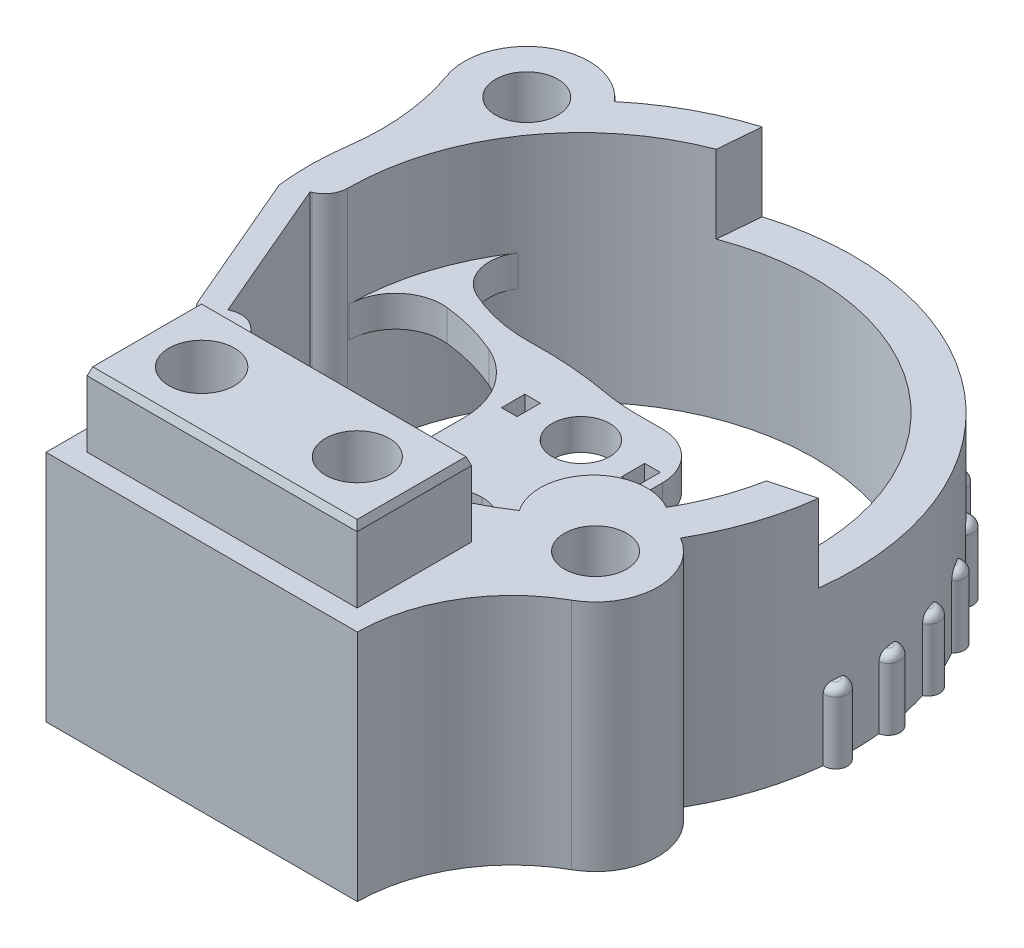
SolidWorks part; units mm, degrees
ref_plane "Спереди" through (0, 0, 0) normal (0, 0, 1) x (1, 0, 0)
ref_plane "Сверху" through (0, 0, 0) normal (0, 1, 0) x (1, 0, 0)
ref_plane "Справа" through (0, 0, 0) normal (1, 0, 0) x (0, 0, -1)
sketch "Sketch1" plane through (0, 0, 0) normal (0, 1, 0) x (1, 0, 0)
  circle A0 centre (0, 0) radius 35
  dimension "D1" = 70
extrude "Boss-Extrude1" add sketch "Sketch1" along normal blind 30
sketch "Sketch6" plane through (0, 30, 0) normal (0, 1, 0) x (1, 0, 0)
  circle A0 centre (0, 0) radius 30
  circle A1 centre (0, 0) radius 35 construction
  dimension "D1" = 5
  dimension "D2" = 60
extrude "Cut-Extrude3" cut sketch "Sketch6" against normal through all
sketch "Sketch7" plane through (0, 30, 0) normal (0, 1, 0) x (1, 0, 0)
  line L0 (0, 0) -> (-22.4976, 26.8116) construction
  line L1 (0, 0) -> (30.3109, -17.5) construction
  line L2 (0, 0) -> (0, -30) construction
  line L3 (0, 0) -> (0, 30) construction
  line L4 (-19.2836, 22.9813) -> (-22.4976, 26.8116)
  line L5 (25.9808, -15) -> (30.3109, -17.5)
  circle A0 centre (0, 0) radius 35 construction
  circle A1 centre (0, 0) radius 30 construction
  arc A2 (-19.2836, 22.9813) -> (25.9808, -15) centre (0, 0) cw
  arc A3 (-22.4976, 26.8116) -> (30.3109, -17.5) centre (0, 0) cw
  dimension "D1" = 40
  dimension "D2" = 60
extrude "Cut-Extrude4" cut sketch "Sketch7" against normal blind 10
sketch "Sketch8" plane through (0, 20, 0) normal (0, 1, 0) x (1, 0, 0)
  line L0 (0, 0) -> (0, -38.8668) construction
  line L3 (10, -33.541) -> (10, 6.459)
  line L4 (10, 6.459) -> (-10, 6.459)
  line L5 (-10, -33.541) -> (-10, 6.459)
  line L6 (10, -33.541) -> (-10, 6.459) construction
  line L7 (10, 6.459) -> (-10, -33.541) construction
  arc A0 (-10, -33.541) -> (10, -33.541) centre (0, 0) ccw
  arc A3 (-22.4976, 26.8116) -> (30.3109, -17.5) centre (0, 0) ccw construction
  point P3 (0, -13.541)
  dimension "D1" = 40
  dimension "D2" = 20
extrude "Boss-Extrude3" add sketch "Sketch8" along normal blind 4 from offset 7 offset against normal yes
sketch "Sketch9" plane through (0, 0, 0) normal (0, -1, 0) x (1, 0, 0)
  line L0 (0, -35) -> (0, 35) construction
  line L2 (-20, 28.7228) -> (20, 28.7228)
  line L3 (-20, 28.7228) -> (-20, 48.7228)
  line L4 (-20, 48.7228) -> (20, 48.7228)
  line L5 (20, 28.7228) -> (20, 48.7228)
  line L6 (-20, 28.7228) -> (20, 48.7228) construction
  line L7 (-20, 48.7228) -> (20, 28.7228) construction
  circle A0 centre (0, 0) radius 35 construction
  point P5 (0, 38.7228)
  dimension "D1" = 40
  dimension "D2" = 20
extrude "Boss-Extrude4" add sketch "Sketch9" against normal up to surface (30 mm away) up to face at (-8.6315, 30, 10.2866)
sketch "Sketch10" plane through (0, 17, 0) normal (0, 1, 0) x (1, 0, 0)
  line L0 (3.7, 0) -> (10, 0) construction
  line L1 (-3.7, 0) -> (-10, 0) construction
  line L2 (8.7, -1.5) -> (6.7, -1.5)
  line L3 (8.7, -1.5) -> (8.7, 1.5)
  line L4 (8.7, 1.5) -> (6.7, 1.5)
  line L5 (6.7, -1.5) -> (6.7, 1.5)
  line L6 (8.7, -1.5) -> (6.7, 1.5) construction
  line L7 (8.7, 1.5) -> (6.7, -1.5) construction
  line L9 (-6.7, -1.5) -> (-8.7, -1.5)
  line L10 (-6.7, -1.5) -> (-6.7, 1.5)
  line L11 (-6.7, 1.5) -> (-8.7, 1.5)
  line L12 (-8.7, -1.5) -> (-8.7, 1.5)
  line L13 (-6.7, -1.5) -> (-8.7, 1.5) construction
  line L14 (-6.7, 1.5) -> (-8.7, -1.5) construction
  circle A0 centre (0, 0) radius 10 construction
  circle A1 centre (0, 0) radius 3.7
  point P6 (7.7, 0)
  point P13 (-7.7, 0)
  dimension "D1" = 20
  dimension "D2" = 7.4
  dimension "D3" = 4
  dimension "D4" = 3
  dimension "D5" = 2
  dimension "D6" = 4
extrude "Cut-Extrude5" cut sketch "Sketch10" against normal through all
sketch "Sketch11" plane through (0, 30, 0) normal (0, 1, 0) x (1, 0, 0)
  line L0 (-20, -38.7228) -> (20, -38.7228) construction
  line L1 (-20, -48.7228) -> (-20, -28.7228) construction
  line L2 (20, -28.7228) -> (20, -48.7228) construction
  circle A0 centre (-10, -38.7228) radius 4.2
  circle A1 centre (10, -38.7228) radius 4.2
  point P10 (0, -38.7228)
  dimension "D1" = 8.4
  dimension "D2" = 20
  dimension "D3" = 10
extrude "Cut-Extrude6" cut sketch "Sketch11" against normal through all
sketch "Sketch15" plane through (0, 30, 0) normal (0, 1, 0) x (1, 0, 0)
  line L0 (19.9782, -38.7228) -> (-20.0306, -38.7228) construction
  line L4 (17.3238, -46.0728) -> (-17.3762, -46.0728)
  line L5 (17.3238, -46.0728) -> (17.3238, -31.3728)
  line L6 (17.3238, -31.3728) -> (-17.3762, -31.3728)
  line L7 (-17.3762, -46.0728) -> (-17.3762, -31.3728)
  line L8 (17.3238, -46.0728) -> (-17.3762, -31.3728) construction
  line L9 (17.3238, -31.3728) -> (-17.3762, -46.0728) construction
  circle A0 centre (-10, -38.7228) radius 4.2
  circle A1 centre (10, -38.7228) radius 4.1
  circle A4 centre (-10, -38.7228) radius 4.2 construction
  point P6 (-0.0262, -38.7228)
  dimension "D1" = 14.7
  dimension "D2" = 34.7
extrude "Boss-Extrude6" add sketch "Sketch15" along normal blind 9.5
chamfer "Chamfer3" distance 1 angle 20 4 edges at (17.3238, 39.5, 38.7228) (-0.0262, 39.5, 46.0728) (-17.3762, 39.5, 38.7228) (-0.0262, 39.5, 31.3728) first distance on face at (17.3238, 34.75, 38.7228) first distance on face at (-0.0262, 34.75, 46.0728) first distance on face at (-17.3762, 34.75, 38.7228) first distance on face at (-0.0262, 34.75, 31.3728)
sketch "Sketch16" plane through (0, 0, 0) normal (0, -1, 0) x (1, 0, 0)
  line L0 (-20, 38.7228) -> (20, 38.7228) construction
  line L1 (-20, 48.7228) -> (-20, 28.7228) construction
  line L2 (20, 28.7228) -> (20, 48.7228) construction
  line L4 (-17.5, 46.2228) -> (17.5, 46.2228)
  line L5 (-17.5, 46.2228) -> (-17.5, 31.2228)
  line L6 (-17.5, 31.2228) -> (17.5, 31.2228)
  line L7 (17.5, 46.2228) -> (17.5, 31.2228)
  line L8 (-17.5, 46.2228) -> (17.5, 31.2228) construction
  line L9 (-17.5, 31.2228) -> (17.5, 46.2228) construction
  point P6 (0, 38.7228)
  dimension "D1" = 15
  dimension "D2" = 35
extrude "Cut-Extrude8" cut sketch "Sketch16" against normal blind 10
chamfer "Chamfer4" distance 1 angle 70 4 edges at (17.5, 0, 38.7228) (0, 0, 46.2228) (-17.5, 0, 38.7228) (0, 0, 31.2228) first distance on face at (0, 0, 38.7228)
sketch "Sketch18" plane through (0, 30, 0) normal (0, 1, 0) x (1, 0, 0)
  line L0 (-31.9117, 14.3752) -> (-22.4976, 26.8116) construction
  line L1 (-22.4976, 26.8116) -> (-19.2836, 22.9813) construction
  line L2 (-31.9117, 14.3752) -> (-27.3529, 12.3216)
  line L3 (-27.3529, 12.3216) -> (-19.2836, 22.9813) construction
  line L4 (-19.2836, 22.9813) -> (-22.4976, 26.8116)
  line L5 (25.9808, -15) -> (30.3109, -17.5) construction
  line L6 (19.6982, -28.9306) -> (16.8841, -24.7977)
  line L7 (25.9808, -15) -> (30.3109, -17.5)
  arc A0 (-22.4976, 26.8116) -> (-31.9117, 14.3752) centre (-28.6259, 21.6693) ccw
  arc A1 (-22.4976, 26.8116) -> (-20, -28.7228) centre (0, 0) ccw construction
  circle A2 centre (-28.6259, 21.6693) radius 4
  arc A3 (-19.2836, 22.9813) -> (-8.6603, -28.7228) centre (0, 0) ccw construction
  arc A4 (-27.3529, 12.3216) -> (-19.2836, 22.9813) centre (-24.5365, 18.5736) ccw
  arc A5 (30.3109, -17.5) -> (19.6982, -28.9306) centre (26.3109, -24.4282) cw
  arc A6 (20, -28.7228) -> (30.3109, -17.5) centre (0, 0) ccw construction
  circle A7 centre (26.3109, -24.4282) radius 4
  arc A8 (25.9808, -15) -> (16.8841, -24.7977) centre (22.5522, -20.9385) ccw
  dimension "D1" = 8
  dimension "D2" = 8
extrude "Boss-Extrude7" add sketch "Sketch18" against normal up to surface (30 mm away) up to face at (0, 0, 38.7228)
sketch "Sketch19" plane through (0, 30, 0) normal (0, 1, 0) x (1, 0, 0)
  circle A0 centre (-28.6259, 21.6693) radius 4
  arc A2 (-25.4189, 24.0599) -> (-30.0563, 17.9337) centre (-28.6259, 21.6693) ccw construction
  circle A3 centre (26.3109, -24.4282) radius 4
  arc A5 (22.8805, -26.4855) -> (28.1083, -20.8548) centre (26.3109, -24.4282) ccw construction
extrude "Cut-Extrude9" cut sketch "Sketch19" against normal through all
chamfer "Chamfer5" distance 10 angle 50 1 edges at (0, 13, 28.7228) first distance on face at (0, 6.5, 28.7228)
fillet "Fillet1" radius 20 1 edges at (0, 13, 16.8053)
sketch "Sketch20" plane through (0, 17, 0) normal (0, 1, 0) x (1, 0, 0)
  line L0 (0, -28.7228) -> (0, -3.7) construction
  line L1 (8.6603, -28.7228) -> (-8.6603, -28.7228) construction
  line L3 (5, -12.7228) -> (-5, -12.7228)
  line L4 (5, -12.7228) -> (5, -28.7228)
  line L5 (5, -28.7228) -> (-5, -28.7228)
  line L6 (-5, -12.7228) -> (-5, -28.7228)
  line L7 (5, -12.7228) -> (-5, -28.7228) construction
  line L8 (5, -28.7228) -> (-5, -12.7228) construction
  circle A0 centre (0, 0) radius 3.7 construction
  point P7 (0, -20.7228)
  dimension "D1" = 10
  dimension "D2" = 16
extrude "Cut-Extrude10" cut sketch "Sketch20" against normal through all
fillet "Fillet3" radius 6 2 edges at (10, 10.184, 28.2843) (-10, 10.184, 28.2843)
fillet "Fillet4" radius 6 2 edges at (10, 15, -6.459) (-10, 15, -6.459)
fillet "Fillet5" radius 5 2 edges at (-5, 14.8714, 12.7228) (5, 14.8714, 12.7228)
sketch "Sketch21" plane through (0, 0, 0) normal (0, -1, 0) x (1, 0, 0)
  circle A0 centre (34.9319, 2.1818) radius 1.5
  arc A1 (-22.4976, -26.8116) -> (30.3109, 17.5) centre (0, 0) ccw construction
  circle A2 centre (34.5618, -4.9512) radius 1.5
  circle A3 centre (32.7339, -11.8559) radius 1.5
  circle A4 centre (29.5261, -18.2377) radius 1.5
  circle A5 centre (25.0754, -23.8242) radius 1.5
  circle A6 centre (19.5717, -28.3768) radius 1.5
  circle A7 centre (13.2499, -31.7013) radius 1.5
  circle A8 centre (6.3799, -33.6559) radius 1.5
  circle A9 centre (-0.7451, -34.157) radius 1.5
  circle A10 centre (-7.821, -33.1833) radius 1.5
  point P26 (0.4047, 0.3972)
  dimension "D1" = 3
  dimension "D2" = 16
  dimension "D4" = 16
  dimension "D3" = 10
extrude "Boss-Extrude8" add sketch "Sketch21" against normal blind 9
fillet "Fillet6" radius 1 10 edges at (36.429, 9, 2.2753) (36.0467, 9, -5.1639) (34.1442, 9, -12.3668) (30.8023, 9, -19.026) (26.1628, 9, -24.8573) (20.4233, 9, -29.6116) (13.8284, 9, -33.0853) (6.6593, 9, -35.1296) (-0.7778, 9, -35.6566) (-8.1651, 9, -34.6433)
fillet "Fillet10" radius 20 1 edges at (20, 15, 29.3448)
fillet "Fillet11" radius 30 1 edges at (-20, 15, 28.7228)
fillet "Fillet12" radius 30 1 edges at (-31.9117, 15, -14.3752)
sketch "Sketch25" plane through (0, 17, 0) normal (0, 1, 0) x (1, 0, 0)
  line L1 (4, 6.459) -> (-4, 6.459) construction
  line L3 (-34.6746, 4.7614) -> (-10, 0.459) construction
  arc A1 (-34.6746, 4.7614) -> (-10, 0.459) centre (-26.054, -18.7053) cw
  arc A2 (0, 6.459) -> (-19.0692, 14.435) centre (1.333, 36.4294) cw
  arc A3 (-27.3529, 12.3216) -> (-19.2836, 22.9813) centre (-24.5365, 18.5736) ccw construction
  arc A4 (-34.6746, 4.7614) -> (-19.0692, 14.435) centre (-22.8002, 3.0297) cw
  arc A5 (-10, 0.459) -> (0, 6.459) centre (4.8429, -12.9458) cw
  point P16 (-19.0692, 14.435)
  dimension "D1" = 30
  dimension "D2" = 25
  dimension "D3" = 12
  dimension "D4" = 20
extrude "Boss-Extrude11" add sketch "Sketch25" against normal up to surface (4 mm away) up to face at (7.7, 13, 0)
fillet "Fillet13" radius 6 1 edges at (-29.379, 15, -6.0726)
fillet "Fillet14" radius 10 1 edges at (-19.0692, 15, -14.435)
fillet "Fillet15" radius 10 1 edges at (-10, 15, -0.459)
sketch "Sketch28" plane through (0, 0, 0) normal (0, -1, 0) x (1, 0, 0)
  line L0 (-19.2836, -22.9813) -> (5.2094, -29.5442)
  arc A0 (-19.2836, -22.9813) -> (-27.3529, -12.3216) centre (0, 0) cw
  arc A1 (-19.2836, -22.9813) -> (-27.3529, -12.3216) centre (-24.5365, -18.5736) ccw construction
  arc A2 (-19.2836, -22.9813) -> (25.9808, 15) centre (0, 0) ccw construction
  arc A3 (-27.3529, -12.3216) -> (5.2094, -29.5442) centre (-14.531, -27.4733) cw
extrude "Cut-Extrude12" cut sketch "Sketch28" against normal through all
fillet "Fillet18" radius 5 1 edges at (-27.3529, 15, -12.3216)
fillet "Fillet19" radius 25 1 edges at (0, 15, -6.459)
sketch "Sketch29" plane through (0, 0, 0) normal (0, -1, 0) x (1, 0, 0)
  line L0 (-26.9231, 22.364) -> (-34.7742, 3.9694)
  line L1 (-26.9231, 22.364) -> (-22.0883, 20.3004) construction
  line L2 (-22.0883, 20.3004) -> (-29.9394, 1.9059) construction
  line L3 (-29.9394, 1.9059) -> (-34.7742, 3.9694) construction
  line L4 (-24.1639, 21.1863) -> (-32.015, 2.7918)
  line L5 (-32.015, 2.7918) -> (-29.9394, 1.9059)
  line L6 (-29.9394, 1.9059) -> (-22.0883, 20.3004)
  line L7 (-22.0883, 20.3004) -> (-24.1639, 21.1863)
  arc A2 (-26.9231, 22.364) -> (-34.6746, -4.7614) centre (0, 0) ccw construction
  arc A3 (-26.9231, 22.364) -> (-34.7742, 3.9694) centre (-30.8486, 13.1667) ccw
  arc A4 (-8.6603, 28.7228) -> (25.9808, 15) centre (0, 0) ccw construction
  dimension "D1" = 20
  dimension "D2" = 3
extrude "Cut-Extrude13" cut sketch "Sketch29" against normal through all
fillet "Fillet20" radius 3 2 edges at (-29.9394, 15, 1.9059) (-22.0883, 15, 20.3004)
fillet "Fillet23" radius 50 1 edges at (-9.2224, 15, -8.3476)
sketch "Sketch30" plane through (0, 20, 0) normal (0, 1, 0) x (1, 0, 0)
  line L0 (-10.1898, 33.4838) -> (-10.659, 28.0426)
  line L1 (34.7446, -4.2206) -> (29.4675, -5.6275)
  line L2 (-22.4976, 26.8116) -> (-19.2836, 22.9813)
  line L4 (30.3109, -17.5) -> (25.9808, -15)
  arc A0 (-22.4976, 26.8116) -> (-10.1898, 33.4838) centre (0, 0) cw
  arc A1 (30.3109, -17.5) -> (-22.4976, 26.8116) centre (0, 0) ccw construction
  arc A2 (30.3109, -17.5) -> (34.7446, -4.2206) centre (0, 0) ccw
  arc A3 (25.9808, -15) -> (-19.2836, 22.9813) centre (0, 0) ccw construction
  arc A4 (-10.659, 28.0426) -> (-19.2836, 22.9813) centre (0, 0) ccw
  arc A5 (25.9808, -15) -> (29.4675, -5.6275) centre (0, 0) ccw
  dimension "D1" = 14
  dimension "D4" = 10
  dimension "D2" = 14
  dimension "D3" = 10
extrude "Boss-Extrude12" add sketch "Sketch30" along normal up to surface (10 mm away) up to face at (-12.3391, 30, 14.0767)
